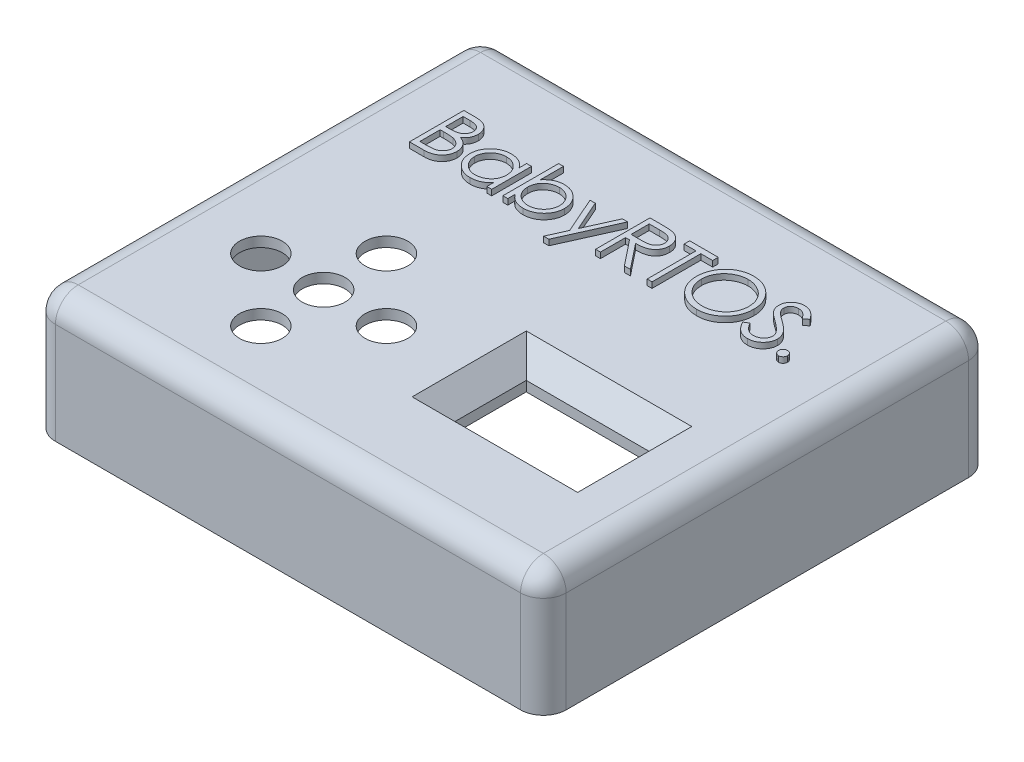
SolidWorks part; units mm, degrees
ref_plane "Front Plane" through (0, 0, 0) normal (0, 0, 1) x (1, 0, 0)
ref_plane "Top Plane" through (0, 0, 0) normal (0, 1, 0) x (1, 0, 0)
ref_plane "Right Plane" through (0, 0, 0) normal (1, 0, 0) x (0, 0, -1)
sketch "Sketch1" plane through (0, 0, 0) normal (0, 1, 0) x (1, 0, 0)
  line L1 (-44.75, 39.25) -> (44.75, 39.25)
  line L2 (-44.75, 39.25) -> (-44.75, -39.25)
  line L3 (-44.75, -39.25) -> (44.75, -39.25)
  line L4 (44.75, 39.25) -> (44.75, -39.25)
  line L5 (-44.75, 39.25) -> (44.75, -39.25) construction
  line L6 (-44.75, -39.25) -> (44.75, 39.25) construction
  point P0 (0, 0)
  dimension "D1" = 78.5
  dimension "D2" = 89.5
extrude "Boss-Extrude1" add sketch "Sketch1" along normal blind 21.75
fillet "Fillet2" radius 4 8 edges at (44.75, 10.875, -39.25) (44.75, 21.75, 0) (0, 21.75, 39.25) (44.75, 10.875, 39.25) (-44.75, 10.875, 39.25) (-44.75, 21.75, 0) (0, 21.75, -39.25) (-44.75, 10.875, -39.25)
sketch "Sketch3" plane through (0, 0, 0) normal (0, 1, 0) x (1, 0, 0)
  line L0 (43, -37.5) -> (31, -19.5) construction
  line L1 (-43, 37.5) -> (43, 37.5) construction
  line L2 (-43, 37.5) -> (-43, -37.5) construction
  line L3 (-43, -37.5) -> (43, -37.5) construction
  line L4 (43, 37.5) -> (43, 33.875) construction
  line L5 (-43, 37.5) -> (43, -37.5) construction
  line L6 (-43, -37.5) -> (43, 37.5) construction
  line L7 (9, -13) -> (31, -13) construction
  line L8 (31, -19.5) -> (9, -19.5)
  line L9 (31, -19.5) -> (31, -6.5)
  line L10 (31, -6.5) -> (9, -6.5)
  line L11 (9, -19.5) -> (9, -6.5)
  line L12 (20, -6.5) -> (20, -19.5) construction
  line L13 (-43, -25.5) -> (-18.5, -25.5) construction
  line L14 (5.5, -3) -> (34.5, -3)
  line L15 (5.5, -3) -> (5.5, -23)
  line L16 (5.5, -23) -> (34.5, -23)
  line L17 (34.5, -3) -> (34.5, -23)
  line L18 (5.5, -3) -> (34.5, -23) construction
  line L19 (5.5, -23) -> (34.5, -3) construction
  line L20 (-18.5, -25.5) -> (-18.5, -37.5) construction
  line L21 (-18.5, -25.5) -> (-18.5, -14.5) construction
  line L22 (-18.5, -14.5) -> (-18.5, -3.5) construction
  line L23 (-18.5, -14.5) -> (-7.5, -14.5) construction
  line L24 (-18.5, -14.5) -> (-29.5, -14.5) construction
  line L25 (44.75, 32.125) -> (41.2124, 32.125)
  line L26 (44.75, -35.25) -> (44.75, 35.25) construction
  line L27 (44.75, 33.875) -> (41.2124, 33.875)
  line L28 (44.75, 33.875) -> (44.75, 32.125)
  line L29 (44.75, 33) -> (38.5, 33) construction
  line L30 (43, 33.875) -> (43, 33) construction
  line L31 (43, 33) -> (43, -37.5) construction
  line L32 (37.625, 35.7124) -> (37.625, 39.25)
  line L33 (40.75, 39.25) -> (-40.75, 39.25) construction
  line L34 (39.375, 35.7124) -> (39.375, 39.25)
  line L35 (37.625, 39.25) -> (39.375, 39.25)
  line L36 (38.5, 39.25) -> (38.5, 33) construction
  circle A0 centre (-18.5, -3.5) radius 3.75
  circle A1 centre (-29.5, -14.5) radius 3.75
  circle A2 centre (-18.5, -14.5) radius 3.75
  circle A3 centre (-7.5, -14.5) radius 3.75
  circle A4 centre (-18.5, -25.5) radius 3.75
  circle A5 centre (38.5, 33) radius 1.1
  arc A6 (41.2124, 33.875) -> (39.375, 35.7124) centre (38.5, 33) ccw
  arc A7 (41.35, 33) -> (41.2124, 33.875) centre (38.5, 33) ccw construction
  arc A8 (41.2124, 32.125) -> (41.35, 33) centre (38.5, 33) ccw construction
  arc A9 (38.5, 35.85) -> (37.625, 35.7124) centre (38.5, 33) ccw construction
  arc A10 (37.625, 35.7124) -> (41.2124, 32.125) centre (38.5, 33) ccw
  arc A11 (39.375, 35.7124) -> (38.5, 35.85) centre (38.5, 33) ccw construction
  point P0 (0, 0)
  point P14 (20, -13)
  dimension "D18" = 7.5
  dimension "D22" = 2.2
  dimension "D17" = 7.5
  dimension "D15" = 7.5
  dimension "D16" = 7.5
  dimension "D19" = 7.5
  dimension "D1" = 86
  dimension "D2" = 75
  dimension "D3" = 18
  dimension "D4" = 12
  dimension "D5" = 22
  dimension "D6" = 13
  dimension "D7" = 29
  dimension "D8" = 20
  dimension "D9" = 24.5
  dimension "D10" = 12
  dimension "D11" = 11
  dimension "D12" = 11
  dimension "D13" = 11
  dimension "D14" = 11
  dimension "D20" = 4.5
  dimension "D21" = 4.5
  dimension "D23" = 1.75
  dimension "D24" = 1.75
  dimension "D25" = 1.75
sketch "Sketch4" plane through (0, 21.75, 0) normal (0, 1, 0) x (1, 0, 0)
  line L0 (5.5, -23) -> (34.5, -23) construction
  line L1 (5.5, -3) -> (5.5, -23) construction
  line L2 (34.5, -3) -> (34.5, -23) construction
  line L3 (5.5, -3) -> (34.5, -3) construction
  line L4 (5.5, -23) -> (34.5, -23)
  line L5 (5.5, -3) -> (5.5, -23)
  line L6 (34.5, -3) -> (34.5, -23)
  line L7 (5.5, -3) -> (34.5, -3)
ref_plane "Plane1" through (0, 17.75, 0) normal (0, 1, 0) x (1, 0, 0)
sketch "Sketch5" plane through (0, 17.75, 0) normal (0, 1, 0) x (1, 0, 0)
  line L0 (31, -19.5) -> (31, -6.5) construction
  line L1 (9, -19.5) -> (9, -6.5) construction
  line L2 (31, -6.5) -> (9, -6.5) construction
  line L3 (31, -19.5) -> (9, -19.5) construction
  line L4 (31, -19.5) -> (31, -6.5)
  line L5 (9, -19.5) -> (9, -6.5)
  line L6 (31, -6.5) -> (9, -6.5)
  line L7 (31, -19.5) -> (9, -19.5)
loft "Cut-Loft1" cut profiles "Sketch4", "Sketch5" connector at (34.5, 21.75, 23) connector at (31, 17.75, 19.5)
shell "Shell1" thickness 1.75 removed face at (0, 0, 0)
extrude "Cut-Extrude1" cut sketch "Sketch3" along normal through all both and the other way through all contours L9 L10 L11 L8
extrude "Cut-Extrude2" cut sketch "Sketch3<4>" along normal through all contours A1 | A2 | A0 | A3 | A4
sketch "Sketch3<4>" plane through (0, 0, 0) normal (0, 1, 0) x (1, 0, 0) same geometry as "Sketch3"
sketch "Sketch6" plane through (0, 0, 0) normal (1, 0, 0) x (0, 0, -1)
  line L0 (37.5, 0) -> (-37.5, 0) construction
  line L1 (35.25, 0) -> (-35.25, 0) construction
  line L2 (37.5, 0) -> (34.5, 0) construction
  line L4 (34.5, 0) -> (22.5, 0)
  line L5 (34.5, 0) -> (34.5, 13)
  line L6 (34.5, 13) -> (22.5, 13)
  line L7 (22.5, 0) -> (22.5, 13)
  point P6 (0, 0)
  dimension "D4" = 12
  dimension "D1" = 75
  dimension "D2" = 3
  dimension "D3" = 13
extrude "Cut-Extrude3" cut sketch "Sketch6" against normal through all
extrude "Boss-Extrude2" add sketch "Sketch3<5>" along normal up to body separate body contours A10 L25 L28 L27 A6 L34 L35 L32 | A5
sketch "Sketch3<5>" plane through (0, 0, 0) normal (0, 1, 0) x (1, 0, 0) same geometry as "Sketch3"
mirror "Mirror1" about plane through (0, 0, 0) normal (0, 0, 1) of "Boss-Extrude2"
sketch "Sketch7" plane through (0, 0, 0) normal (0, 1, 0) x (1, 0, 0)
  line L0 (37.625, 35.7124) -> (37.625, 39.25) construction
  line L1 (37.625, 39.25) -> (39.375, 39.25) construction
  line L2 (39.375, 35.7124) -> (39.375, 39.25) construction
  line L3 (44.75, 33.875) -> (41.2124, 33.875) construction
  line L4 (44.75, 33.875) -> (44.75, 32.125) construction
  line L5 (44.75, 32.125) -> (41.2124, 32.125) construction
  line L12 (-37.625, -35.7124) -> (-37.625, -39.25)
  line L13 (37.625, 35.7124) -> (37.625, 39.25)
  line L14 (37.625, 39.25) -> (39.375, 39.25)
  line L15 (39.375, 35.7124) -> (39.375, 39.25)
  line L16 (44.75, 33.875) -> (41.2124, 33.875)
  line L17 (44.75, 33.875) -> (44.75, 32.125)
  line L18 (44.75, 32.125) -> (41.2124, 32.125)
  line L19 (-37.625, -39.25) -> (-39.375, -39.25)
  line L20 (-39.375, -35.7124) -> (-39.375, -39.25)
  line L21 (-44.75, -33.875) -> (-41.2124, -33.875)
  line L22 (-44.75, -33.875) -> (-44.75, -32.125)
  line L23 (-44.75, -32.125) -> (-41.2124, -32.125)
  line L25 (-44.75, 22.5) -> (-44.75, -35.25) construction
  line L26 (-40.75, -39.25) -> (40.75, -39.25) construction
  circle A0 centre (38.5, 33) radius 1.1 construction
  arc A1 (41.2124, 33.875) -> (39.375, 35.7124) centre (38.5, 33) ccw construction
  arc A4 (37.625, 35.7124) -> (41.2124, 32.125) centre (38.5, 33) ccw construction
  circle A6 centre (38.5, 33) radius 1.1
  arc A7 (41.2124, 33.875) -> (39.375, 35.7124) centre (38.5, 33) ccw
  arc A8 (37.625, 35.7124) -> (41.2124, 32.125) centre (38.5, 33) ccw
  circle A9 centre (-38.5, -33) radius 1.1
  arc A10 (-41.2124, -33.875) -> (-39.375, -35.7124) centre (-38.5, -33) ccw
  arc A11 (-37.625, -35.7124) -> (-41.2124, -32.125) centre (-38.5, -33) ccw
  dimension "D1" = 2
extrude "Boss-Extrude3" add sketch "Sketch7" along normal up to body separate body contours A11 L23 L22 L21 A10 L20 L19 L12 | A9
fillet "Fillet3" radius 2 2 edges at (-43.875, 0, -22.5) (-43.875, 0, -34.5)
sketch "Sketch8" plane through (0, 21.75, 0) normal (0, 1, 0) x (1, 0, 0)
  text T0 "BabyRTOS." font "Century Gothic" height in points 36
extrude "Boss-Extrude4" add sketch "Sketch8" along normal blind 1
equation "\"T\"= 1.75"
equation "\"PCB_W\"= 86"
equation "\"PCB_H\"= 75"
equation "\"D2@Sketch1\"=\"PCB_W\"+\"T\"*2"
equation "\"D1@Sketch1\"=\"PCB_H\"+\"T\"*2"
equation "\"Fillet\"= 4"
equation "\"D1@Fillet2\"=\"Fillet\""
equation "\"Z_Offset\"= 20"
equation "\"D1@Boss-Extrude1\"=\"Z_Offset\"+\"T\""
equation "\"D1@Shell1\"=\"T\""
equation "\"D1@Sketch3\"=\"PCB_W\""
equation "\"D2@Sketch3\"=\"PCB_H\""
equation "\"OLED_X_Offset\"= 12"
equation "\"OLED_Y_Offset\"= 18"
equation "\"OLED_W\"= 22"
equation "\"OLED_H\"= 13"
equation "\"D5@Sketch3\"=\"OLED_W\""
equation "\"D6@Sketch3\"=\"OLED_H\""
equation "\"D4@Sketch3\"=\"OLED_X_Offset\""
equation "\"D3@Sketch3\"=\"OLED_Y_Offset\""
equation "\"D7@Sketch3\"=\"OLED_W\" + \"OLED_Space\""
equation "\"D8@Sketch3\"=\"OLED_H\"+\"OLED_Space\""
equation "\"OLED_Space\"= 7"
equation "\"BUTTON_D\"= 7.5"
equation "\"D1@Sketch6\"=\"PCB_H\""
equation "\"D24@Sketch3\"=\"T\""
equation "\"D18@Sketch3\"=\"BUTTON_D\""
equation "\"D17@Sketch3\"=\"BUTTON_D\""
equation "\"D15@Sketch3\"=\"BUTTON_D\""
equation "\"D16@Sketch3\"=\"BUTTON_D\""
equation "\"D19@Sketch3\"=\"BUTTON_D\""
